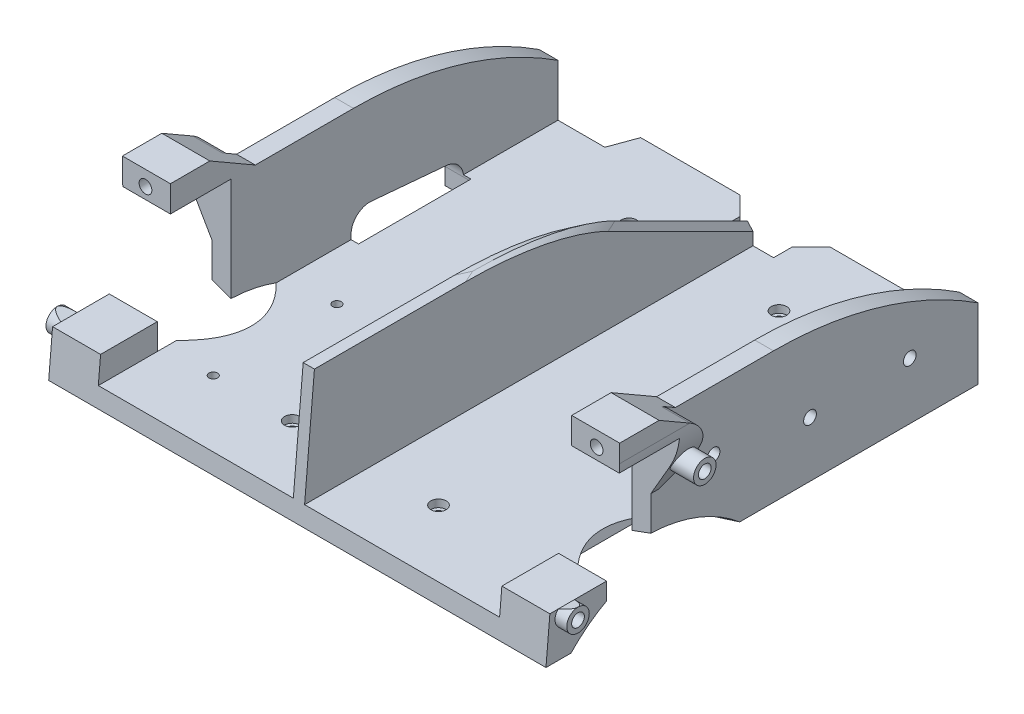
SolidWorks part; units mm, degrees
ref_plane "Ebene vorne" through (0, 0, 0) normal (0, 0, 1) x (1, 0, 0)
ref_plane "Ebene oben" through (0, 0, 0) normal (0, 1, 0) x (1, 0, 0)
ref_plane "Ebene rechts" through (0, 0, 0) normal (1, 0, 0) x (0, 0, -1)
sketch "Skizze1" plane through (0, 0, 0) normal (0, 1, 0) x (1, 0, 0)
  line L10 (56.5, -65) -> (-56.5, -65)
  line L11 (56.5, -65) -> (56.5, 65)
  line L12 (56.5, 65) -> (-56.5, 65)
  line L13 (-56.5, -65) -> (-56.5, 65)
  line L14 (56.5, -65) -> (-56.5, 65) construction
  line L15 (56.5, 65) -> (-56.5, -65) construction
  point P0 (0, 0)
  dimension "D1" = 130
  dimension "D2" = 113
extrude "Aufsatz-Linear austragen1" add sketch "Skizze1" along normal blind 5
sketch "Skizze2" plane through (0, 5, 0) normal (0, 1, 0) x (1, 0, 0)
  line L0 (-27.5, 73.3788) -> (-27.5, -80.6083) construction
  line L1 (-56.5, 65) -> (-53.5, 65)
  line L2 (-56.5, 65) -> (-56.5, -65)
  line L3 (-56.5, -65) -> (-53.5, -65)
  line L4 (-53.5, 65) -> (-53.5, -65)
  line L5 (0, 65) -> (0, -65) construction
  line L6 (56.5, 65) -> (-56.5, 65) construction
  line L7 (53.5, 65) -> (53.5, -65)
  line L8 (56.5, -65) -> (53.5, -65)
  line L9 (56.5, 65) -> (56.5, -65)
  line L10 (56.5, 65) -> (53.5, 65)
  line L11 (-1.5, 65) -> (-1.5, -65)
  line L12 (-56.5, -65) -> (56.5, -65) construction
  line L13 (1.5, -65) -> (-1.5, -65)
  line L14 (1.5, 65) -> (1.5, -65)
  line L15 (1.5, 65) -> (-1.5, 65)
  line L16 (-56.5, 65) -> (-56.5, -65) construction
  dimension "D1" = 3
  dimension "D2" = 3
  dimension "D3" = 3
extrude "Aufsatz-Linear austragen2" add sketch "Skizze2" along normal blind 30
ref_plane "Ebene2" through (0, 0, 0) normal (-1, 0, 0) x (0, 0, 1)
sketch "Skizze6" plane through (0, -42.1377, 3.6866) normal (0, 0.9962, -0.0872) x (1, 0, 0)
  line L5 (-56.5, -67.8031) -> (56.5, -67.8031)
  line L6 (-56.5, -67.8031) -> (-56.5, -64.7527)
  line L7 (-56.5, -64.7527) -> (56.5, -64.7527)
  line L8 (56.5, -67.8031) -> (56.5, -64.7527)
extrude "Schnitt-Linear austragen4" cut sketch "Skizze6" along normal through all
sketch "Skizze8" plane through (56.5, 0, 0) normal (1, 0, 0) x (0, 0, -1)
  line L0 (-29.2379, 35) -> (-29.2379, 11.9)
  line L1 (-61.9379, 35) -> (65, 35) construction
  line L2 (-29.2379, 11.9) -> (-45.3379, 11.9)
  line L3 (-45.3379, 11.9) -> (-45.3379, 6.9)
  line L4 (-45.3379, 6.9) -> (-48.8379, 6.9)
  line L5 (-48.8379, 6.9) -> (-48.8379, 11.9)
  line L6 (-48.8379, 11.9) -> (-63.9589, 11.9)
  line L7 (-61.9379, 35) -> (-65, 0) construction
  line L8 (-63.9589, 11.9) -> (-61.9379, 35)
  line L9 (-61.9379, 35) -> (-29.2379, 35)
  line L10 (-47.0879, 7.4) -> (-47.0879, 6.9) construction
  line L11 (-45.9379, 7.4) -> (-48.2379, 7.4) construction
  line L12 (-45.8379, 12.3) -> (-45.8379, 7.5) construction
  line L13 (-45.7379, 12.4) -> (-35.7379, 12.4) construction
  line L14 (-29.7379, 15.5937) -> (-29.7379, 31.8063) construction
  dimension "D1" = 0.5
  dimension "D2" = 0.5
  dimension "D3" = 0.5
  dimension "D4" = 0.5
extrude "Schnitt-Linear austragen6" cut sketch "Skizze8" against normal blind 10
mirror "Spiegeln2" about plane through (0, 0, 0) normal (-1, 0, 0) of "Schnitt-Linear austragen6"
sketch "Skizze10" plane through (0, 0, 48.3379) normal (0, 0, 1) x (1, 0, 0)
  line L0 (-66.3, 7.5) -> (-66.3, 12.3) construction
  line L1 (-53.5, 11.9) -> (-66.3, 11.9)
  line L2 (-53.5, 11.9) -> (-53.5, 0)
  line L3 (-53.5, 0) -> (-66.3, 0)
  line L4 (-66.3, 11.9) -> (-66.3, 0)
  line L6 (-56.5, 0) -> (56.5, 0) construction
  line L7 (0, -14.1421) -> (0, -24.0994) construction
  line L8 (66.3, 11.9) -> (66.3, 0)
  line L9 (53.5, 0) -> (66.3, 0)
  line L10 (53.5, 11.9) -> (53.5, 0)
  line L11 (53.5, 11.9) -> (66.3, 11.9)
  line L12 (53.5, 11.9) -> (53.5, 5) construction
extrude "Aufsatz-Linear austragen3" add sketch "Skizze10" along normal up to surface (15.121 mm away) from offset 0.5
sketch "Skizze12" plane through (0, 0, 45.8379) normal (0, 0, -1) x (-1, 0, 0)
  line L0 (66.3, 35.1) -> (66.3, 39.9) construction
  line L1 (53.5, 42) -> (66.3, 42)
  line L2 (53.5, 42) -> (53.5, 35)
  line L3 (53.5, 35) -> (66.3, 35)
  line L4 (66.3, 42) -> (66.3, 35)
  line L5 (59.65, 40) -> (54.1, 40) construction
  line L6 (0, 35) -> (0, 43.6638) construction
  line L7 (-1.5, 35) -> (1.5, 35) construction
  line L8 (-66.3, 42) -> (-66.3, 35)
  line L9 (-53.5, 35) -> (-66.3, 35)
  line L10 (-53.5, 42) -> (-53.5, 35)
  line L11 (-53.5, 42) -> (-66.3, 42)
  dimension "D1" = 2
extrude "Aufsatz-Linear austragen4" add sketch "Skizze12" along normal offset from surface (26.1 mm away) 10 from offset 0.5 up to face at (-55, 23.45, 29.2379) offset beyond the face yes
sketch "Skizze13" plane through (0, 42, 0) normal (0, 1, 0) x (1, 0, 0)
  line L0 (-53.5, -19.2379) -> (-53.5, -45.3379) construction
  line L1 (-66.3, -19.2379) -> (-53.5, -19.2379)
  line L2 (-66.3, -19.2379) -> (-66.3, -29.2379)
  line L3 (-66.3, -29.2379) -> (-53.5, -29.2379)
  line L4 (-53.5, -19.2379) -> (-53.5, -29.2379)
  line L5 (-63.1063, -29.7379) -> (-57.1937, -29.7379) construction
  line L6 (0, 0) -> (0, -67.6923) construction
  line L7 (53.5, -19.2379) -> (53.5, -29.2379)
  line L8 (66.3, -29.2379) -> (53.5, -29.2379)
  line L9 (66.3, -19.2379) -> (66.3, -29.2379)
  line L10 (66.3, -19.2379) -> (53.5, -19.2379)
  dimension "D1" = 0.5
extrude "Aufsatz-Linear austragen6" add sketch "Skizze13" against normal offset from surface (27 mm away) 20 up to face at (-55, 35, -22.8811)
chamfer "Fase1" distance 16.9 angle 30 4 edges at (-61.4, 15, 19.2379) (-66.3, 15, 24.2379) (61.4, 15, 19.2379) (66.3, 15, 24.2379)
chamfer "Fase3" distance 9 angle 60 2 edges at (-59.9, 42, 19.2379) (59.9, 42, 19.2379)
fillet "Verrundung7" radius 1.5 2 edges at (-61.4, 33, 19.2379) (61.4, 33, 19.2379)
fillet "Verrundung8" radius 20 2 edges at (-66.3, 31.9, 24.2379) (66.3, 31.9, 24.2379)
ref_plane "Ebene1" through (-48.8487, 17.7795, 0) normal (-0.9397, 0.342, 0) x (0, 0, -1)
sketch "Skizze14" plane through (0, 0, 48.8379) normal (0, 0, -1) x (-1, 0, 0)
  line L0 (0, 35) -> (0, 43.2744) construction
  line L1 (-1.5, 35) -> (1.5, 35) construction
  circle A0 centre (60.15, 9.4) radius 1.7
  circle A1 centre (-60.15, 9.4) radius 1.7
  arc A2 (-59.65, 8.2544) -> (-60.65, 8.2544) centre (-60.15, 9.4) ccw construction
  dimension "D1" = 3.4
extrude "Schnitt-Linear austragen8" cut sketch "Skizze14" against normal blind 4
sketch "Skizze15" plane through (0, 0, 45.3379) normal (0, 0, 1) x (1, 0, 0)
  line L0 (0, 35) -> (0, 41.2956) construction
  line L1 (-1.5, 35) -> (1.5, 35) construction
  circle A0 centre (60.15, 38) radius 1.7
  circle A1 centre (-60.15, 38) radius 1.7
  arc A2 (59.65, 39.1456) -> (60.65, 39.1456) centre (60.15, 38) ccw construction
  dimension "D1" = 3.4
extrude "Schnitt-Linear austragen9" cut sketch "Skizze15" against normal blind 4
sketch "Skizze16" plane through (-56.5, 0, 0) normal (-1, 0, 0) x (0, 0, 1)
  line L0 (34.8264, 42) -> (26.6147, 37.259) construction
  line L1 (28.9951, 15) -> (19.2379, 31.9) construction
  line L2 (23.2616, 24.9308) -> (18.7616, 32.725)
  line L3 (18.7616, 32.725) -> (26.5558, 37.225)
  line L6 (26.6147, 37.259) -> (19.9879, 33.433) construction
  line L7 (28.9951, 15) -> (21.9174, 27.259) construction
  arc A0 (23.2616, 24.9308) -> (26.5558, 37.225) centre (31.0558, 29.4308) cw
  dimension "D1" = 9
extrude "Schnitt-Linear austragen10" cut sketch "Skizze16" along normal through all
mirror "Spiegeln4" about plane through (0, 0, 0) normal (-1, 0, 0) of "Schnitt-Linear austragen10"
sketch "Skizze20" plane through (-56.5, 0, 0) normal (-1, 0, 0) x (0, 0, 1)
  line L0 (29.2379, 27.259) -> (22.3218, 27.259) construction
  circle A0 centre (25.7798, 27.259) radius 3
  dimension "D1" = 6
extrude "Aufsatz-Linear austragen8" add sketch "Skizze20" along normal up to surface (12.93 mm away)
sketch "Skizze21" plane through (-69.43, 0, 0) normal (-1, 0, 0) x (0, 0, 1)
  circle A0 centre (25.7798, 27.259) radius 1.7
  dimension "D1" = 3.4
extrude "Schnitt-Linear austragen12" cut sketch "Skizze21" against normal blind 4
sketch "Skizze23" plane through (-56.5, 0, 0) normal (-1, 0, 0) x (0, 0, 1)
  line L0 (-65, 5) -> (-5, 35)
  line L1 (-65, 35) -> (22.702, 35) construction
  line L2 (-5, 35) -> (-65, 35)
  line L3 (-65, 35) -> (-65, 5)
  dimension "D1" = 60
extrude "Schnitt-Linear austragen15" cut sketch "Skizze23" along normal up to surface (3 mm away) from surface at -58 up to face at (-1.5, 20, -0.8749) starting at face at (1.5, 20, -0.8749)
chamfer "Fase4" distance 1.5 angle 45 2 edges at (1.5, 20, -35) (-1.5, 20, -35)
fillet "Verrundung9" radius 20 2 edges at (0.75, 35, -3.3229) (-0.75, 35, -3.3229)
sketch "Skizze24" plane through (0, 5, 0) normal (0, 1, 0) x (1, 0, 0)
  line L0 (-37.5, -30.4263) -> (-39.4501, -30.4263) construction
  line L1 (-37.5, -13.9439) -> (-37.5, -46.9087) construction
  circle A0 centre (-40.5, -13.9439) radius 1.15
  circle A1 centre (-40.5, -46.9087) radius 1.15
  dimension "D1" = 2.3
extrude "Schnitt-Linear austragen16" cut sketch "Skizze24" against normal through all
sketch "Skizze25" plane through (0, 5, 0) normal (0, 1, 0) x (1, 0, 0)
  line L0 (0, -64.0565) -> (0, -52.1701) construction
  line L1 (-36.2072, -25.2732) -> (15.0029, -25.2732) construction
  line L2 (0, 13.5101) -> (0, 1.6238) construction
  circle A0 centre (19.5, -46.8553) radius 1.15
  circle A1 centre (-19.5, -46.8553) radius 1.15
  circle A2 centre (-19.5, -46.8553) radius 1.7 construction
  circle A3 centre (19.5, -46.8553) radius 1.7 construction
  circle A4 centre (-19.5, -3.6911) radius 1.15
  circle A5 centre (19.5, -3.6911) radius 1.15
  circle A6 centre (-19.5, -3.6911) radius 1.7 construction
  dimension "D1" = 2.3
extrude "Schnitt-Linear austragen17" cut sketch "Skizze25" against normal through all
sketch "Skizze28" plane through (-66.3, 0, 0) normal (-1, 0, 0) x (0, 0, 1)
  circle A0 centre (59.5831, 9.8244) radius 3
  circle A1 centre (59.5831, 9.8244) radius 3 construction
extrude "Aufsatz-Linear austragen9" add sketch "Skizze28" along normal up to surface (3.13 mm away)
ref_plane "Ebene3" through (0, 0, 63.9589) normal (0, 0, -1) x (-1, 0, 0)
sketch "Skizze22" plane through (-69.43, 0, 0) normal (-1, 0, 0) x (0, 0, 1)
  circle A0 centre (59.5831, 9.8244) radius 1.7
  circle A1 centre (59.5831, 9.8244) radius 1.25 construction
  dimension "D1" = 3.4
extrude "Schnitt-Linear austragen14" cut sketch "Skizze22" against normal blind 4
sketch "Skizze32" plane through (-69.43, 0, 0) normal (-1, 0, 0) x (0, 0, 1)
  circle A0 centre (25.7798, 27.259) radius 3
  arc A1 (28.7798, 27.259) -> (22.7798, 27.259) centre (25.7798, 27.259) ccw construction
extrude "Aufsatz-Linear austragen10" add sketch "Skizze32" against normal up to surface (12.93 mm away) from surface at -125.93 starting at face at (56.5, 16.7032, 17.983)
sketch "Skizze33" plane through (66.3, 0, 0) normal (1, 0, 0) x (0, 0, -1)
  circle A0 centre (-59.5831, 9.8244) radius 3
  circle A1 centre (-59.5831, 9.8244) radius 3 construction
extrude "Aufsatz-Linear austragen11" add sketch "Skizze33" along normal up to surface (3.13 mm away) up to face at (69.43, 27.259, 22.7798)
sketch "Skizze31" plane through (0, 0, 63.9589) normal (0, 0, -1) x (-1, 0, 0)
  line L0 (66.3, 11.9) -> (69.43, 12.8244)
  line L1 (0, 40.8746) -> (0, 10.8244) construction
  line L3 (66.3, 12.8244) -> (66.3, 11.9)
  line L4 (69.43, 6.8244) -> (69.43, 12.8244) construction
  line L6 (69.43, 12.8244) -> (66.3, 12.8244)
  line L7 (66.3, 12.8244) -> (66.3, 11.9) construction
  line L8 (53.5, 11.9) -> (66.3, 11.9) construction
  line L9 (-69.43, 12.8244) -> (-66.3, 12.8244)
  line L10 (-66.3, 12.8244) -> (-66.3, 11.9)
  line L11 (-66.3, 11.9) -> (-69.43, 12.8244)
  line L12 (0, 5) -> (0, 27.6491) construction
extrude "Schnitt-Linear austragen22" cut sketch "Skizze31" along normal through all
sketch "Skizze34" plane through (69.43, 0, 0) normal (1, 0, 0) x (0, 0, -1)
  line L0 (-52.8385, 38.2347) -> (-25.634, -14.511) construction
  circle A0 centre (-25.7798, 27.259) radius 1.7
  circle A1 centre (-59.5831, 9.8244) radius 1.7
  dimension "D1" = 3.4
extrude "Schnitt-Linear austragen23" cut sketch "Skizze34" against normal blind 4
sketch "Skizze35" plane through (0, 5, 0) normal (0, 1, 0) x (1, 0, 0)
  line L0 (0, 41.8903) -> (0, 49.2883) construction
  circle A0 centre (20, 43.4251) radius 1.15
  circle A1 centre (-20, 43.4251) radius 1.15
  dimension "D1" = 2.3
extrude "Schnitt-Linear austragen24" cut sketch "Skizze35" against normal through all
sketch "Skizze36" plane through (0, 5, 0) normal (0, 1, 0) x (1, 0, 0)
  line L0 (0, 65) -> (0, 19.7018) construction
  line L1 (-7, 65) -> (7, 65)
  line L2 (-7, 65) -> (-7, 55)
  line L3 (-7, 55) -> (7, 55)
  line L4 (7, 65) -> (7, 55)
  line L5 (-7, 65) -> (7, 55) construction
  line L6 (-7, 55) -> (7, 65) construction
  line L7 (53.5, 65) -> (0, 65) construction
  line L8 (5, 43.6172) -> (5, 84.6533) construction
  point P0 (0, 60)
  dimension "D1" = 2
  dimension "D2" = 10
extrude "Schnitt-Linear austragen25" cut sketch "Skizze36" against normal through all and the other way through all
sketch "Skizze37" plane through (-56.5, 0, 0) normal (-1, 0, 0) x (0, 0, 1)
  line L0 (-65, 35) -> (-65, 0)
  line L1 (-65, 0) -> (45.7053, 0)
  line L2 (45.7053, 0) -> (45.3379, 11.9)
  line L3 (45.3379, 11.9) -> (29.2379, 11.9)
  line L4 (29.2379, 11.9) -> (29.2379, 24.259)
  line L5 (29.2379, 24.259) -> (23.6902, 24.259)
  line L8 (-65, 35) -> (22.702, 35) construction
  line L9 (22.702, 35) -> (-65, 35)
  line L11 (34.8264, 42) -> (26.6147, 37.259) construction
  line L12 (26.5558, 37.225) -> (22.702, 35)
  line L14 (22.3218, 27.259) -> (22.8674, 25.6958)
  line L16 (22.8674, 25.6958) -> (24.2597, 26.3308) construction
  line L17 (23.6902, 24.259) -> (22.8674, 25.6958)
  arc A0 (22.3218, 27.259) -> (26.5558, 37.225) centre (31.0558, 29.4308) cw
  arc A1 (26.5558, 37.225) -> (22.3218, 27.259) centre (31.0558, 29.4308) ccw construction
  arc A2 (26.5558, 37.225) -> (23.2616, 24.9308) centre (31.0558, 29.4308) ccw construction
  arc A3 (22.7798, 27.259) -> (28.7798, 27.259) centre (25.7798, 27.259) ccw construction
  arc A6 (22.3218, 27.259) -> (23.2616, 24.9308) centre (31.0558, 29.4308) ccw construction
extrude "Aufsatz-Linear austragen12" add sketch "Skizze37" along normal blind 2
sketch "Skizze38" plane through (56.5, 0, 0) normal (1, 0, 0) x (0, 0, -1)
  line L0 (65, 35) -> (65, 0)
  line L1 (65, 0) -> (-45.3379, 0)
  line L2 (-45.3379, 0) -> (-45.3379, 11.9)
  line L3 (-45.3379, 11.9) -> (-29.2379, 11.9)
  line L4 (-29.2379, 11.9) -> (-29.2379, 24.259)
  line L5 (-29.2379, 24.259) -> (-23.6494, 24.259)
  line L6 (-23.2616, 24.9308) -> (-28.9951, 15) construction
  line L8 (-23.2616, 24.9308) -> (-28.9951, 15) construction
  line L10 (-26.5558, 37.225) -> (-22.702, 35)
  line L11 (-22.702, 35) -> (65, 35)
  line L12 (-26.5558, 37.225) -> (-22.702, 35) construction
  line L13 (-24.0662, 26.2372) -> (-22.8633, 25.7048) construction
  line L14 (-22.3218, 27.259) -> (-22.8633, 25.7048)
  line L15 (-23.6494, 24.259) -> (-22.8633, 25.7048)
  arc A0 (-23.2616, 24.9308) -> (-26.5558, 37.225) centre (-31.0558, 29.4308) ccw construction
  arc A1 (-22.3218, 27.259) -> (-26.5558, 37.225) centre (-31.0558, 29.4308) ccw
  arc A2 (-22.3218, 27.259) -> (-26.5558, 37.225) centre (-31.0558, 29.4308) ccw construction
  circle A3 centre (-25.7798, 27.259) radius 3 construction
extrude "Aufsatz-Linear austragen13" add sketch "Skizze38" along normal blind 2
sketch "Skizze4" plane through (-48.8487, 17.7795, 0) normal (-0.9397, 0.342, 0) x (0, 0, -1)
  line L0 (-30.4263, 72.2703) -> (-30.4263, 51.3241) construction
  line L2 (-45.7053, 19.3241) -> (-48.8379, 19.3241) construction
  circle A0 centre (-30.4263, 51.3241) radius 40
  ellipse E0 centre (-30.4263, 72.2703) end of major axis (-3.1974, 72.2719) minor radius 25.5846 construction
  dimension "D1" = 80
  dimension "D2" = 32
extrude "Schnitt-Linear austragen2" cut sketch "Skizze4" against normal blind 10 and the other way through all
mirror "Spiegeln1" about plane through (0, 0, 0) normal (-1, 0, 0) of "Schnitt-Linear austragen2"
sketch "Skizze27" plane through (-56.5, 0, 0) normal (-1, 0, 0) x (0, 0, 1)
  line L0 (-18.5975, -0.0672) -> (-17.0614, 0.0672) construction
  line L1 (-17.337, -14.4748) -> (-16.5883, -23.0321) construction
  line L2 (-17.8294, 0) -> (-17.4658, -4.1568) construction
  line L3 (-15.0522, -22.8977) -> (-15.8009, -14.3404) construction
  line L4 (-23.198, -14.6965) -> (-17.3623, -14.1859) construction
  line L5 (-65, 0) -> (5.5403, 0) construction
  line L6 (-32.8294, 9.0201) -> (-2.8294, 11.6448)
  line L7 (-32.8294, 9.0201) -> (-32.8294, 0)
  line L8 (-32.8294, 0) -> (-2.8294, 0)
  line L9 (-2.8294, 11.6448) -> (-2.8294, 0)
  line L10 (-40.6109, 8.3393) -> (12.7398, 13.0069) construction
  dimension "D1" = 30
  dimension "D2" = 10
extrude "Schnitt-Linear austragen18" cut sketch "Skizze27" against normal blind 5 and the other way through all from surface at 0 starting at face at (-56.5, 5.7335, 47.1813)
sketch "Skizze40" plane through (-58.5, 0, 0) normal (-1, 0, 0) x (0, 0, 1)
  line L0 (-65, 13.9938) -> (-35, 35)
  line L2 (22.702, 35) -> (-65, 35) construction
  line L3 (-35, 35) -> (-65, 35)
  line L4 (-65, 35) -> (-65, 13.9938)
  line L7 (-65, 35) -> (-65, 0) construction
  line L9 (-32.8294, 5) -> (-65, 5) construction
  dimension "D1" = 35
  dimension "D2" = 30
extrude "Schnitt-Linear austragen26" cut sketch "Skizze40" against normal up to surface (5 mm away) up to face at (-53.5, 16.9243, 19.1544)
sketch "Skizze41" plane through (-58.5, 0, 0) normal (-1, 0, 0) x (0, 0, 1)
  line L0 (-65, 13.9938) -> (-65, 35)
  line L1 (-65, 35) -> (-35, 35)
  line L2 (-35, 35) -> (-65, 13.9938)
extrude "Schnitt-Linear austragen27" cut sketch "Skizze41" against normal through all from surface at -112 starting at face at (53.5, 19.2388, 28.4003)
sketch "Skizze42" plane through (0, 5, 0) normal (0, 1, 0) x (1, 0, 0)
  line L0 (-7, 65) -> (-53.5, 65) construction
  line L1 (-41, 65) -> (-46, 65)
  line L2 (-41, 65) -> (-41, 58)
  line L3 (-41, 58) -> (-46, 58)
  line L4 (-46, 65) -> (-46, 58)
  line L5 (-41, 65) -> (-46, 58) construction
  line L6 (-41, 58) -> (-46, 65) construction
  line L7 (-43.5, 61.1953) -> (-43.5, 61.5) construction
  line L8 (-45, 61.1953) -> (-42, 61.1953) construction
  line L9 (-42, 61.1953) -> (-42, 90.1036) construction
  line L10 (0, 55) -> (0, 63.2057) construction
  line L11 (43.5, 61.1953) -> (43.5, 61.5) construction
  line L12 (41, 58) -> (46, 65) construction
  line L13 (41, 65) -> (46, 58) construction
  line L14 (46, 65) -> (46, 58)
  line L15 (41, 58) -> (46, 58)
  line L16 (41, 65) -> (41, 58)
  line L17 (41, 65) -> (46, 65)
  line L18 (0, 55) -> (0, 19.7018) construction
  line L19 (-1.5, 55) -> (0, 55) construction
  point P0 (-43.5, 61.5)
  point P21 (43.5, 61.5)
  dimension "D1" = 1
  dimension "D2" = 7
extrude "Schnitt-Linear austragen28" cut sketch "Skizze42" against normal through all
chamfer "Fase5" distance 5 angle 45 2 edges at (7, 2.5, -65) (-7, 2.5, -65)
chamfer "Fase6" distance 7 angle 20 12 edges at (-46, 0, -61.5) (-46, 2.5, -65) (-41, 0, -61.5) (-41, 2.5, -65) (-46, 5, -61.5) (-41, 5, -61.5) (41, 0, -61.5) (41, 2.5, -65) (46, 0, -61.5) (46, 2.5, -65) (41, 5, -61.5) (46, 5, -61.5)
fillet "Verrundung10" radius 100 2 edges at (-56, 35, -35) (56, 35, -35)
sketch "Skizze43" plane through (0, 5, 0) normal (0, 1, 0) x (1, 0, 0)
  line L0 (0, 98.2107) -> (0, 75.2245) construction
  line L1 (58.5, 58) -> (46, 58)
  line L2 (58.5, 58) -> (58.5, 65)
  line L3 (58.5, 65) -> (46, 65)
  line L4 (46, 58) -> (46, 65)
  line L5 (-46, 58) -> (-46, 65)
  line L6 (-58.5, 65) -> (-46, 65)
  line L7 (-58.5, 58) -> (-58.5, 65)
  line L8 (-58.5, 58) -> (-46, 58)
extrude "Schnitt-Linear austragen29" cut sketch "Skizze43" against normal through all and the other way through all
sketch "Skizze44" plane through (58.5, 0, 0) normal (1, 0, 0) x (0, 0, -1)
  line L0 (0.5597, 18.1689) -> (-0.1532, 13.8193) construction
  line L2 (26.6605, 4.0392) -> (26.4907, 16.4092) construction
  circle A0 centre (-12.5215, 18.9693) radius 1.7
  circle A1 centre (13.2121, 14.7517) radius 1.7
  circle A2 centre (39.8098, 15.1169) radius 1.7
  dimension "D1" = 3.4
extrude "Schnitt-Linear austragen30" cut sketch "Skizze44" against normal blind 4
mirror "Spiegeln5" about plane through (0, 0, 0) normal (-1, 0, 0) of "Schnitt-Linear austragen30"
sketch "Skizze45" plane through (0, 0, 0) normal (0, -1, 0) x (-1, 0, 0)
  line L0 (-53.5, -43.7252) -> (-53.5, -17.1274) construction
  line L1 (-66.3, -48.8379) -> (-56.5, -48.8379) construction
  line L2 (-58.5, -29.2379) -> (-53.5, -29.2379)
  line L3 (-58.5, -29.2379) -> (-58.5, -48.8379)
  line L4 (-58.5, -48.8379) -> (-53.5, -48.8379)
  line L5 (-53.5, -29.2379) -> (-53.5, -48.8379)
  line L6 (0, 0) -> (0, -34.1739) construction
  line L7 (53.5, -29.2379) -> (53.5, -48.8379)
  line L8 (58.5, -48.8379) -> (53.5, -48.8379)
  line L9 (58.5, -29.2379) -> (58.5, -48.8379)
  line L10 (58.5, -29.2379) -> (53.5, -29.2379)
extrude "Schnitt-Linear austragen31" cut sketch "Skizze45" against normal up to surface (11.9 mm away) up to face at (56, 11.9, 37.2879)
sketch "Skizze46" plane through (0, 5, 0) normal (0, 1, 0) x (1, 0, 0)
  line L0 (0, 50.4199) -> (0, 23.3558) construction
  line L1 (-20.0607, 19.8637) -> (-6.9702, 20.0026) construction
  line L2 (-32.4661, -25.2732) -> (-12.0867, -25.2732) construction
  circle A0 centre (20, 43.4251) radius 2.05
  circle A1 centre (-20, 43.4251) radius 2.05
  circle A8 centre (-19.5, -3.6911) radius 2.05
  circle A9 centre (19.5, -3.6911) radius 2.05
  circle A10 centre (-19.5, -46.8553) radius 2.05
  circle A11 centre (19.5, -46.8553) radius 2.05
  dimension "D1" = 4.1
extrude "Schnitt-Linear austragen32" cut sketch "Skizze46" against normal blind 2
fillet "Verrundung11" radius 5 2 edges at (-56, 11.6448, -2.8294) (-56, 9.0201, -32.8294)
equation "\"M2EinschmelzGewindeDurchmesser\"=3.4"
equation "\"M2EinschmelzGewindeTiefe\"= 4.0"
equation "\"M3EinschmelzGewindeDurchmesser\"= 4.2"
equation "\"M3EinschmelzGewindeTief\"= 5.7"
equation "\"M2SchraubeLoch\"=2.3"
equation "\"offSetVonGummiReifen\"= 3.0"
equation "\"D1@Schnitt-Linear austragen8\"=\"M2EinschmelzGewindeTiefe\""
equation "\"D1@Skizze14\"=\"M2EinschmelzGewindeDurchmesser\""
equation "\"D1@Skizze15\"=\"M2EinschmelzGewindeDurchmesser\""
equation "\"D1@Schnitt-Linear austragen9\"=\"M2EinschmelzGewindeTiefe\""
equation "\"D1@Skizze21\"=\"M2EinschmelzGewindeDurchmesser\""
equation "\"D1@Schnitt-Linear austragen12\"=\"M2EinschmelzGewindeTiefe\""
equation "\"D1@Schnitt-Linear austragen13\"=\"M2EinschmelzGewindeTiefe\""
equation "\"D1@Skizze22\"=\"M2EinschmelzGewindeDurchmesser\""
equation "\"D1@Schnitt-Linear austragen14\"=\"M2EinschmelzGewindeTiefe\""
equation "\"D1@Skizze24\"=\"M2SchraubeLoch\""
equation "\"D1@Skizze25\"=\"M2SchraubeLoch\""
equation "\"D1@Skizze34\"=\"M2EinschmelzGewindeDurchmesser\""
equation "\"D1@Schnitt-Linear austragen23\"=\"M2EinschmelzGewindeTiefe\""
equation "\"D1@Skizze35\"=\"M2SchraubeLoch\""
equation "\"D1@Skizze44\"=\"M2EinschmelzGewindeDurchmesser\""
equation "\"D1@Schnitt-Linear austragen30\"=\"M2EinschmelzGewindeTiefe\""
